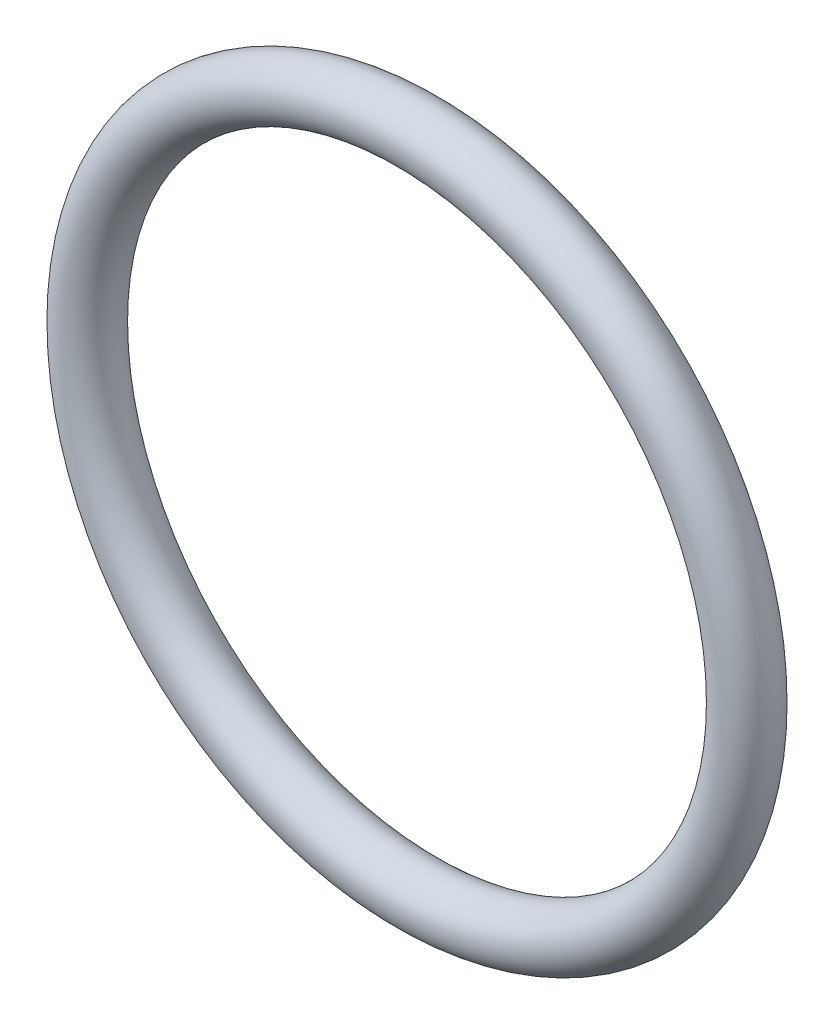
SolidWorks part; units mm, degrees
ref_plane "Front Plane" through (0, 0, 0) normal (0, 0, 1) x (1, 0, 0)
ref_plane "Top Plane" through (0, 0, 0) normal (0, 1, 0) x (1, 0, 0)
ref_plane "Right Plane" through (0, 0, 0) normal (1, 0, 0) x (0, 0, -1)
sketch "Sketch1" plane through (0, 0, 0) normal (0, 1, 0) x (1, 0, 0)
  line L0 (0, 0.889) -> (0, -0.889) construction
  circle A0 centre (10.2743, 0) radius 0.889
revolve "Revolve1" add sketch "Sketch1" angle 360 about L0 reverse direction yes
ref_axis "Axis1" through (0, 0, -0.9779) along (0, 0, 1)
sketch "Sketch2" plane through (0, 0, 0) normal (0, 1, 0) x (1, 0, 0)
  arc A0 (10.2743, -0.889) -> (10.2743, 0.889) centre (10.2743, 0) ccw construction
  arc A1 (10.2743, -0.889) -> (10.2743, 0.889) centre (10.2743, 0) ccw
